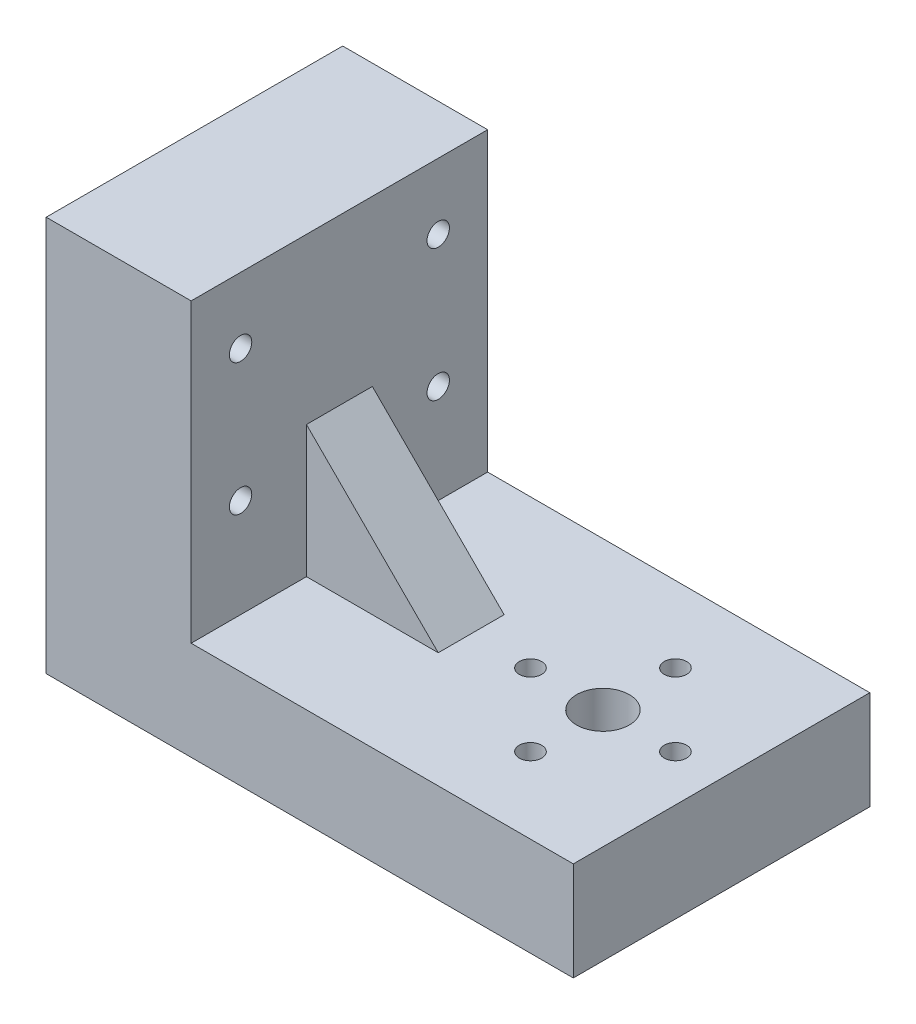
SolidWorks part; units mm, degrees
material "PETG"
ref_plane "Front Plane" through (0, 0, 0) normal (0, 0, 1) x (1, 0, 0)
ref_plane "Top Plane" through (0, 0, 0) normal (0, 1, 0) x (1, 0, 0)
ref_plane "Right Plane" through (0, 0, 0) normal (1, 0, 0) x (0, 0, -1)
sketch "Sketch1" plane through (0, 0, 0) normal (0, 0, 1) x (1, 0, 0)
  line L1 (0, 0) -> (22, 0)
  line L2 (0, 0) -> (0, 60)
  line L3 (0, 60) -> (22, 60)
  line L4 (22, 0) -> (22, 60)
  dimension "D1" = 22
  dimension "D2" = 60
sketch "Sketch2" plane through (0, 0, 0) normal (0, 0, 1) x (1, 0, 0)
  line L1 (0, 0) -> (80, 0)
  line L2 (0, 0) -> (0, 15)
  line L3 (0, 15) -> (80, 15)
  line L4 (80, 0) -> (80, 15)
  dimension "D1" = 80
  dimension "D2" = 15
extrude "Boss-Extrude3" add sketch "Sketch1" along normal blind 22.5 and the other way blind 22.5
extrude "Boss-Extrude4" add sketch "Sketch2" along normal blind 22.5 and the other way blind 22.5
sketch "Sketch3" plane through (0, 0, 0) normal (0, 1, 0) x (1, 0, 0)
  circle A0 centre (62, 0) radius 4
  circle A1 centre (73, 0) radius 1.7
  circle A2 centre (51, 0) radius 1.7
  circle A3 centre (62, 11) radius 1.7
  circle A4 centre (62, -11) radius 1.7
extrude "Cut-Extrude1" cut sketch "Sketch3" against normal through all and the other way through all
sketch "Sketch4" plane through (0, 0, 0) normal (1, 0, 0) x (0, 0, -1)
  circle A0 centre (15, 30) radius 1.7
  circle A1 centre (-15, 30) radius 1.7
  circle A2 centre (15, 50) radius 1.7
  circle A3 centre (-15, 50) radius 1.7
extrude "Cut-Extrude2" cut sketch "Sketch4" against normal through all and the other way through all
sketch "Sketch5" plane through (0, 0, 0) normal (0, 0, 1) x (1, 0, 0)
  line L0 (22, 15) -> (42, 15)
  line L1 (42, 15) -> (22, 35)
  line L2 (22, 35) -> (22, 15)
extrude "Boss-Extrude5" add sketch "Sketch5" along normal blind 5 and the other way blind 5
equation "\"P\" = 300"
equation "\"n\" = 3"
equation "\"E\" = 2000"
equation "\"Sy\" = 45"
equation "\"delta_max\" = 0.3"
equation "\"b\" = 45"
equation "\"L1\" = 40"
equation "\"Lp\" = 58"
equation "\"H\" = 45"
equation "\"sigma_allow\" = \"Sy\" / \"n\""
equation "\"I_req1\" = \"P\" * \"L1\" ^ 3 / ( 3 * \"E\" * \"delta_max\" )"
equation "\"h1\" = int ( ( 12 * \"I_req1\" / \"b\" ) ^ ( 1 / 3 ) ) + 1"
equation "\"M_tr\" = \"P\" * \"L1\""
equation "\"I_req2\" = ( \"P\" * \"H\" ^ 3 / 3 + \"M_tr\" * \"H\" ^ 2 / 2 ) / ( \"E\" * \"delta_max\" )"
equation "\"t2\" = int ( ( 12 * \"I_req2\" / \"b\" ) ^ ( 1 / 3 ) ) + 1"
equation "\"L_total\" = \"t2\" + \"Lp\""
equation "\"H_total\" = \"H\" + \"h1\""
equation "\"D1@Sketch1\" = \"t2\""
equation "\"D2@Sketch1\" = \"H_total\""
equation "\"D1@Sketch2\" = \"L_total\""
equation "\"D2@Sketch2\" = \"h1\""
equation "\"d_bolt\" = 3.4"
equation "\"d_shaft\" = 8"
